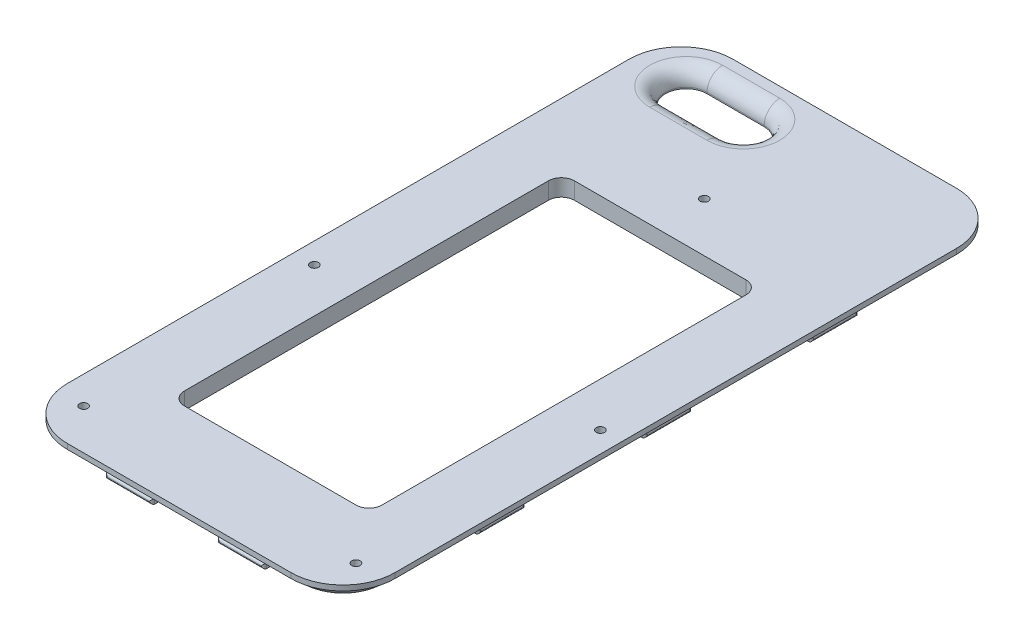
SolidWorks part; units mm, degrees
ref_plane "Front Plane" through (0, 0, 0) normal (0, 0, 1) x (1, 0, 0)
ref_plane "Top Plane" through (0, 0, 0) normal (0, 1, 0) x (1, 0, 0)
ref_plane "Right Plane" through (0, 0, 0) normal (1, 0, 0) x (0, 0, -1)
sketch "Sketch2" plane through (0, 0, 0) normal (0, 1, 0) x (1, 0, 0)
  line L4 (-51.1712, 92.3697) -> (-51.1712, -15.6303)
  line L5 (-41.1712, -25.6303) -> (1.8288, -25.6303)
  line L6 (11.8288, 92.3697) -> (11.8288, -15.6303)
  line L7 (-41.1712, 102.3697) -> (1.8288, 102.3697)
  arc A4 (-51.1712, -15.6303) -> (-41.1712, -25.6303) centre (-41.1712, -15.6303) ccw
  arc A5 (11.8288, -15.6303) -> (1.8288, -25.6303) centre (1.8288, -15.6303) cw
  arc A6 (1.8288, 102.3697) -> (11.8288, 92.3697) centre (1.8288, 92.3697) cw
  arc A7 (-51.1712, 92.3697) -> (-41.1712, 102.3697) centre (-41.1712, 92.3697) cw
extrude "Boss-Extrude1" add sketch "Sketch2" along normal blind 1
sketch "Sketch3" plane through (0, 0, 0) normal (0, -1, 0) x (1, 0, 0)
  line L8 (-41.1712, -100.3697) -> (1.8288, -100.3697)
  line L9 (9.8288, -92.3697) -> (9.8288, 15.6303)
  line L10 (1.8288, 23.6303) -> (-41.1712, 23.6303)
  line L11 (-49.1712, 15.6303) -> (-49.1712, -92.3697)
  line L12 (-41.1712, -100.3697) -> (1.8288, -100.3697)
  line L13 (9.8288, -92.3697) -> (9.8288, 15.6303)
  line L14 (1.8288, 23.6303) -> (-41.1712, 23.6303)
  line L15 (-49.1712, 15.6303) -> (-49.1712, -92.3697)
  arc A8 (-49.1712, -92.3697) -> (-41.1712, -100.3697) centre (-41.1712, -92.3697) ccw
  arc A9 (1.8288, -100.3697) -> (9.8288, -92.3697) centre (1.8288, -92.3697) ccw
  arc A10 (9.8288, 15.6303) -> (1.8288, 23.6303) centre (1.8288, 15.6303) ccw
  arc A11 (-41.1712, 23.6303) -> (-49.1712, 15.6303) centre (-41.1712, 15.6303) ccw
  arc A12 (-49.1712, -92.3697) -> (-41.1712, -100.3697) centre (-41.1712, -92.3697) ccw
  arc A13 (1.8288, -100.3697) -> (9.8288, -92.3697) centre (1.8288, -92.3697) ccw
  arc A14 (9.8288, 15.6303) -> (1.8288, 23.6303) centre (1.8288, 15.6303) ccw
  arc A15 (-41.1712, 23.6303) -> (-49.1712, 15.6303) centre (-41.1712, 15.6303) ccw
  dimension "D1" = 2
extrude "Boss-Extrude2" add sketch "Sketch3" along normal blind 2.25
sketch "Sketch4" plane through (0, 0, -100.3697) normal (0, 0, -1) x (-1, 0, 0)
  line L0 (19.6712, -2.25) -> (-1.8288, -2.25) construction
  line L1 (41.1712, -2.25) -> (-1.8288, -2.25) construction
  line L2 (19.6712, -2.25) -> (41.1712, -2.25) construction
  line L3 (30.4212, -2.25) -> (30.4212, -1.75) construction
  line L4 (8.9212, -2.25) -> (8.9212, -1.75) construction
  line L6 (34.9212, -1.25) -> (25.9212, -1.25)
  line L7 (34.9212, -1.25) -> (34.9212, -2.25)
  line L8 (34.9212, -2.25) -> (25.9212, -2.25)
  line L9 (25.9212, -1.25) -> (25.9212, -2.25)
  line L10 (34.9212, -1.25) -> (25.9212, -2.25) construction
  line L11 (34.9212, -2.25) -> (25.9212, -1.25) construction
  line L12 (13.4212, -1.25) -> (4.4212, -1.25)
  line L13 (13.4212, -1.25) -> (13.4212, -2.25)
  line L14 (13.4212, -2.25) -> (4.4212, -2.25)
  line L15 (4.4212, -1.25) -> (4.4212, -2.25)
  line L16 (13.4212, -1.25) -> (4.4212, -2.25) construction
  line L17 (13.4212, -2.25) -> (4.4212, -1.25) construction
extrude "Boss-Extrude3" add sketch "Sketch4" along normal blind 1
fillet "Fillet1" radius 0.5 8 edges at (-8.9212, -2.25, -101.3697) (-4.4212, -1.75, -101.3697) (-13.4212, -1.75, -101.3697) (-8.9212, -1.25, -101.3697) (-25.9212, -1.75, -101.3697) (-30.4212, -1.25, -101.3697) (-30.4212, -2.25, -101.3697) (-34.9212, -1.75, -101.3697)
sketch "Sketch5" plane through (0, 0, 23.6303) normal (0, 0, 1) x (1, 0, 0)
  line L0 (-19.6712, -2.25) -> (-41.1712, -2.25) construction
  line L1 (1.8288, -2.25) -> (-41.1712, -2.25) construction
  line L2 (-19.6712, -2.25) -> (1.8288, -2.25) construction
  line L3 (-8.9212, -2.25) -> (-8.9212, -1.75) construction
  line L4 (-30.4212, -2.25) -> (-30.4212, -1.75) construction
  line L6 (-4.4212, -1.25) -> (-13.4212, -1.25)
  line L7 (-4.4212, -1.25) -> (-4.4212, -2.25)
  line L8 (-4.4212, -2.25) -> (-13.4212, -2.25)
  line L9 (-13.4212, -1.25) -> (-13.4212, -2.25)
  line L10 (-4.4212, -1.25) -> (-13.4212, -2.25) construction
  line L11 (-4.4212, -2.25) -> (-13.4212, -1.25) construction
  line L12 (-25.9212, -1.25) -> (-34.9212, -1.25)
  line L13 (-25.9212, -1.25) -> (-25.9212, -2.25)
  line L14 (-25.9212, -2.25) -> (-34.9212, -2.25)
  line L15 (-34.9212, -1.25) -> (-34.9212, -2.25)
  line L16 (-25.9212, -1.25) -> (-34.9212, -2.25) construction
  line L17 (-25.9212, -2.25) -> (-34.9212, -1.25) construction
extrude "Boss-Extrude4" add sketch "Sketch5" along normal blind 1
fillet "Fillet2" radius 0.5 8 edges at (-30.4212, -1.25, 24.6303) (-30.4212, -2.25, 24.6303) (-34.9212, -1.75, 24.6303) (-25.9212, -1.75, 24.6303) (-8.9212, -1.25, 24.6303) (-8.9212, -2.25, 24.6303) (-13.4212, -1.75, 24.6303) (-4.4212, -1.75, 24.6303)
sketch "Sketch6" plane through (-49.1712, 0, 0) normal (-1, 0, 0) x (0, 0, 1)
  line L0 (-38.3697, -2.25) -> (-92.3697, -2.25) construction
  line L1 (15.6303, -2.25) -> (-92.3697, -2.25) construction
  line L2 (-38.3697, -2.25) -> (15.6303, -2.25) construction
  line L3 (-11.3697, -2.25) -> (-10.8697, -2.25) construction
  line L4 (-10.8697, -2.25) -> (-10.8697, -1.25) construction
  line L5 (-10.8697, -1.25) -> (-1.8697, -1.25) construction
  line L6 (-65.3697, -2.25) -> (-66.3697, -2.25) construction
  line L7 (-66.3697, -2.25) -> (-66.3697, -1.25) construction
  line L8 (-66.3697, -1.25) -> (-75.3697, -1.25) construction
  line L9 (-38.3697, -2.25) -> (-38.3697, -1.75) construction
  line L10 (-10.8697, -2.25) -> (-10.8697, -1.25)
  line L11 (-33.8697, -1.25) -> (-42.8697, -1.25)
  line L12 (-33.8697, -1.25) -> (-33.8697, -2.25)
  line L13 (-33.8697, -2.25) -> (-42.8697, -2.25)
  line L14 (-42.8697, -1.25) -> (-42.8697, -2.25)
  line L15 (-33.8697, -1.25) -> (-42.8697, -2.25) construction
  line L16 (-33.8697, -2.25) -> (-42.8697, -1.25) construction
  line L17 (-10.8697, -2.25) -> (-1.8697, -2.25)
  line L18 (-10.8697, -1.25) -> (-1.8697, -1.25)
  line L19 (-1.8697, -2.25) -> (-1.8697, -1.25)
  line L20 (-66.3697, -2.25) -> (-66.3697, -1.25)
  line L21 (-66.3697, -2.25) -> (-75.3697, -2.25)
  line L22 (-66.3697, -1.25) -> (-75.3697, -1.25)
  line L23 (-75.3697, -2.25) -> (-75.3697, -1.25)
extrude "Boss-Extrude5" add sketch "Sketch6" along normal blind 0.6
fillet "Fillet3" radius 0.5 12 edges at (-49.7712, -1.25, -70.8697) (-49.7712, -1.75, -75.3697) (-49.7712, -2.25, -70.8697) (-49.7712, -1.75, -66.3697) (-49.7712, -1.75, -42.8697) (-49.7712, -1.25, -38.3697) (-49.7712, -2.25, -38.3697) (-49.7712, -1.75, -33.8697) (-49.7712, -1.75, -10.8697) (-49.7712, -2.25, -6.3697) (-49.7712, -1.25, -6.3697) (-49.7712, -1.75, -1.8697)
sketch "Sketch7" plane through (9.8288, 0, 0) normal (1, 0, 0) x (0, 0, -1)
  line L0 (38.3697, -2.25) -> (-15.6303, -2.25) construction
  line L1 (92.3697, -2.25) -> (-15.6303, -2.25) construction
  line L2 (38.3697, -2.25) -> (92.3697, -2.25) construction
  line L3 (65.3697, -2.25) -> (65.8697, -2.25) construction
  line L4 (65.8697, -2.25) -> (65.8697, -1.25) construction
  line L5 (65.8697, -1.25) -> (74.8697, -1.25) construction
  line L6 (65.8697, -2.25) -> (65.8697, -1.25)
  line L7 (65.8697, -2.25) -> (74.8697, -2.25)
  line L8 (65.8697, -1.25) -> (74.8697, -1.25)
  line L9 (74.8697, -2.25) -> (74.8697, -1.25)
  line L10 (38.3697, -2.25) -> (38.3697, -1.75) construction
  line L11 (11.3697, -2.25) -> (10.8697, -2.25) construction
  line L12 (42.8697, -1.25) -> (33.8697, -1.25)
  line L13 (42.8697, -1.25) -> (42.8697, -2.25)
  line L14 (42.8697, -2.25) -> (33.8697, -2.25)
  line L15 (33.8697, -1.25) -> (33.8697, -2.25)
  line L16 (42.8697, -1.25) -> (33.8697, -2.25) construction
  line L17 (42.8697, -2.25) -> (33.8697, -1.25) construction
  line L18 (10.8697, -2.25) -> (10.8697, -1.25) construction
  line L19 (10.8697, -1.25) -> (1.8697, -1.25) construction
  line L20 (10.8697, -2.25) -> (10.8697, -1.25)
  line L21 (10.8697, -2.25) -> (1.8697, -2.25)
  line L22 (10.8697, -1.25) -> (1.8697, -1.25)
  line L23 (1.8697, -2.25) -> (1.8697, -1.25)
extrude "Boss-Extrude6" add sketch "Sketch7" along normal blind 0.6
fillet "Fillet4" radius 0.5 12 edges at (10.4288, -1.75, -1.8697) (10.4288, -1.25, -6.3697) (10.4288, -1.75, -10.8697) (10.4288, -2.25, -6.3697) (10.4288, -1.75, -33.8697) (10.4288, -1.25, -38.3697) (10.4288, -2.25, -38.3697) (10.4288, -1.75, -42.8697) (10.4288, -1.75, -65.8697) (10.4288, -1.25, -70.3697) (10.4288, -2.25, -70.3697) (10.4288, -1.75, -74.8697)
sketch "Sketch8" plane through (0, -2.25, 0) normal (0, -1, 0) x (1, 0, 0)
  line L0 (-30.1712, -89.3697) -> (-41.1712, -89.3697)
  line L1 (-41.1712, -89.3697) -> (-30.1712, -89.3697) construction
  line L3 (-41.1712, -97.3697) -> (-30.1712, -97.3697)
  arc A1 (-30.1712, -97.3697) -> (-30.1712, -89.3697) centre (-30.1712, -93.3697) ccw
  arc A2 (-41.1712, -97.3697) -> (-41.1712, -89.3697) centre (-41.1712, -93.3697) cw
extrude "Cut-Extrude1" cut sketch "Sketch8" against normal blind 4
sketch "Sketch9" plane through (0, -2.25, 0) normal (0, -1, 0) x (1, 0, 0)
  line L0 (1.8288, 23.6303) -> (1.8288, 15.6303) construction
  line L1 (-41.1712, 23.6303) -> (-41.1712, 15.6303) construction
  line L5 (-0.6712, -64.3697) -> (-0.6712, 5.6303)
  line L7 (-3.1712, 8.1303) -> (-36.1712, 8.1303)
  line L8 (-38.6712, -64.3697) -> (-38.6712, 5.6303)
  line L9 (-3.1712, -66.8697) -> (-36.1712, -66.8697)
  arc A0 (9.8288, 15.6303) -> (1.8288, 23.6303) centre (1.8288, 15.6303) ccw construction
  arc A5 (-0.6712, 5.6303) -> (-3.1712, 8.1303) centre (-3.1712, 5.6303) ccw
  arc A6 (-36.1712, 8.1303) -> (-38.6712, 5.6303) centre (-36.1712, 5.6303) ccw
  arc A7 (-38.6712, -64.3697) -> (-36.1712, -66.8697) centre (-36.1712, -64.3697) ccw
  arc A8 (-0.6712, -64.3697) -> (-3.1712, -66.8697) centre (-3.1712, -64.3697) cw
extrude "Cut-Extrude2" cut sketch "Sketch9" against normal blind 4
fillet "Fillet6" radius 1 18 edges at (9.8288, -2.25, 6.8803) (7.4857, -2.25, 21.2872) (-38.0462, -2.25, 23.6303) (-46.828, -2.25, 21.2872) (-49.1712, -2.25, -83.8697) (-46.828, -2.25, -98.0265) (-1.2962, -2.25, -100.3697) (9.8288, -2.25, -83.6197) (9.8288, -2.25, -22.3697) (9.8288, -2.25, -54.3697) (-1.2962, -2.25, 23.6303) (-19.6712, -2.25, 23.6303) (-49.1712, -2.25, 6.8803) (-49.1712, -2.25, -22.3697) (-49.1712, -2.25, -54.6197) (-38.0462, -2.25, -100.3697) (-19.6712, -2.25, -100.3697) (7.4857, -2.25, -98.0265)
fillet "Fillet7" radius 3 4 edges at (-26.1712, 1, -93.3697) (-35.6712, 1, -97.3697) (-45.1712, 1, -93.3697) (-35.6712, 1, -89.3697)
sketch "Sketch12" plane through (0, 1, 0) normal (0, 1, 0) x (1, 0, 0)
  circle A0 centre (-20.6712, 76.3597) radius 0.8
  circle A1 centre (7.8288, 27.8597) radius 0.8
  circle A2 centre (6.5088, -17.8203) radius 0.8
  circle A3 centre (-45.8512, -17.8203) radius 0.8
  circle A4 centre (-47.1712, 27.8597) radius 0.8
extrude "Cut-Extrude5" cut sketch "Sketch12" against normal blind 12
chamfer "Chamfer3" distance 1.5 angle 30 3 edges at (6.5088, -2.25, 17.0203) (-45.8512, -2.25, 17.0203) (-20.6712, -2.25, -77.1597) first distance on face at (-47.1712, -2.25, -28.6597)
chamfer "Chamfer4" distance 1.5 angle 30 2 edges at (-47.1712, -2.25, -28.6597) (7.8288, -2.25, -28.6597) first distance on face at (-20.6712, -2.25, -78.6597)
